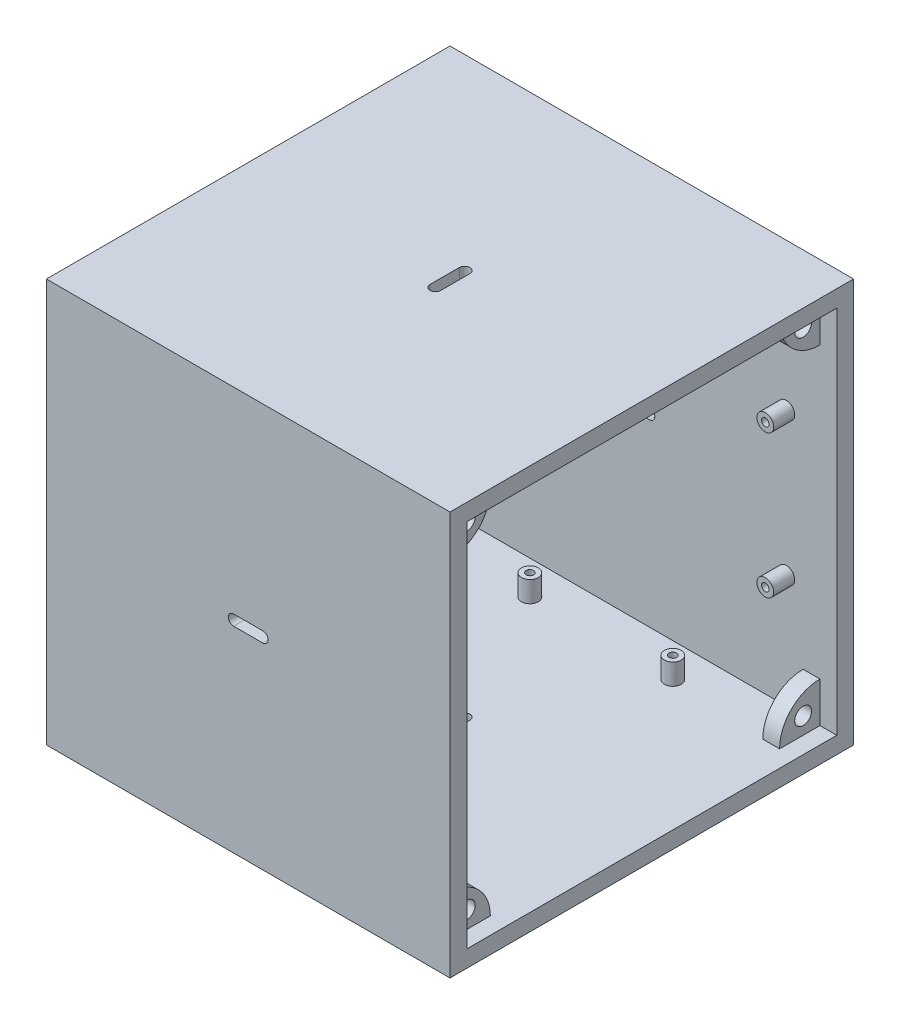
SolidWorks part; units mm, degrees
ref_plane "Front Plane" through (0, 0, 0) normal (0, 0, 1) x (1, 0, 0)
ref_plane "Top Plane" through (0, 0, 0) normal (0, 1, 0) x (1, 0, 0)
ref_plane "Right Plane" through (0, 0, 0) normal (1, 0, 0) x (0, 0, -1)
sketch "Sketch1" plane through (0, 0, 0) normal (0, 1, 0) x (1, 0, 0)
  line L1 (-76.2, -76.2) -> (76.2, -76.2)
  line L2 (-76.2, -76.2) -> (-76.2, 76.2)
  line L3 (-76.2, 76.2) -> (76.2, 76.2)
  line L4 (76.2, -76.2) -> (76.2, 76.2)
  line L5 (-76.2, -76.2) -> (76.2, 76.2) construction
  line L6 (-76.2, 76.2) -> (76.2, -76.2) construction
  point P0 (0, 0)
  dimension "D1" = 152.4
  dimension "D2" = 152.4
extrude "Boss-Extrude1" add sketch "Sketch1" along normal blind 152.4
shell "Shell2" thickness 6.35
ref_plane "Symmetry Top Plane" through (0, 76.2, 0) normal (0, 1, 0) x (1, 0, 0)
sketch "Sketch2" plane through (-69.85, 0, 0) normal (1, 0, 0) x (0, 0, -1)
  line L0 (-5.5, 76.2) -> (5.5, 76.2) construction
  line L1 (-7.5, 74.2) -> (7.5, 74.2) construction
  line L2 (-7.5, 74.2) -> (-7.5, 78.2) construction
  line L3 (-7.5, 78.2) -> (7.5, 78.2) construction
  line L4 (7.5, 74.2) -> (7.5, 78.2) construction
  line L5 (-7.5, 74.2) -> (7.5, 78.2)
  line L6 (-7.5, 78.2) -> (7.5, 74.2)
  line L7 (-5.5, 78.2) -> (5.5, 78.2)
  line L8 (-5.5, 74.2) -> (5.5, 74.2)
  line L10 (19, 73.2) -> (31, 73.2)
  line L11 (19, 73.2) -> (19, 79.2)
  line L12 (19, 79.2) -> (31, 79.2)
  line L13 (31, 73.2) -> (31, 79.2)
  line L14 (19, 73.2) -> (31, 79.2) construction
  line L15 (19, 79.2) -> (31, 73.2) construction
  line L16 (-31, 73.2) -> (-19, 73.2)
  line L17 (-31, 73.2) -> (-31, 79.2)
  line L18 (-31, 79.2) -> (-19, 79.2)
  line L19 (-19, 73.2) -> (-19, 79.2)
  line L20 (-31, 73.2) -> (-19, 79.2) construction
  line L21 (-31, 79.2) -> (-19, 73.2) construction
  arc A0 (-5.5, 78.2) -> (-5.5, 74.2) centre (-5.5, 76.2) ccw
  arc A1 (5.5, 74.2) -> (5.5, 78.2) centre (5.5, 76.2) ccw
  point P0 (0, 76.2)
  point P8 (0, 76.2)
  point P13 (-7.5, 76.2)
  point P14 (7.5, 76.2)
  point P15 (25, 76.2)
  point P20 (-25, 76.2)
  dimension "D6" = 2
  dimension "D1" = 15
  dimension "D2" = 4
  dimension "D3" = 76.2
  dimension "D4" = 0
  dimension "D5" = 25
  dimension "D7" = 15
  dimension "D8" = 12
  dimension "D9" = 6
  dimension "D10" = 25
  dimension "D11" = 25
  dimension "D12" = 6
  dimension "D13" = 12
  dimension "D14" = 25
extrude "Cut-Extrude3" cut sketch "Sketch2" along direction (1, 0, 0) on the side against the normal blind 6.35 contours L8 A1 L6 L5 A0 | L6 A1 L5 | L5 A1 L7 A0 L6 | L6 A0 L5 | L18 L19 L16 L17 | L12 L13 L10 L11
sketch "Sketch3" plane through (0, 0, -69.85) normal (0, 0, 1) x (1, 0, 0)
  line L0 (-5.5, 76.2) -> (5.5, 76.2) construction
  line L1 (-7.5, 74.2) -> (7.5, 74.2) construction
  line L2 (-7.5, 74.2) -> (-7.5, 78.2) construction
  line L3 (-7.5, 78.2) -> (7.5, 78.2) construction
  line L4 (7.5, 74.2) -> (7.5, 78.2) construction
  line L5 (-7.5, 74.2) -> (7.5, 78.2)
  line L6 (-7.5, 78.2) -> (7.5, 74.2)
  line L7 (-5.5, 78.2) -> (5.5, 78.2)
  line L8 (-5.5, 74.2) -> (5.5, 74.2)
  arc A0 (-5.5, 78.2) -> (-5.5, 74.2) centre (-5.5, 76.2) ccw
  arc A1 (5.5, 74.2) -> (5.5, 78.2) centre (5.5, 76.2) ccw
  point P0 (0, 76.2)
  point P7 (0, 76.2)
  point P12 (-7.5, 76.2)
  point P13 (7.5, 76.2)
  dimension "D3" = 2
  dimension "D6" = 76.2
  dimension "D1" = 15
  dimension "D2" = 4
  dimension "D4" = 15
  dimension "D5" = 0
extrude "Cut-Extrude4" cut sketch "Sketch3" against normal blind 6.35 contours L8 A1 L7 A0
sketch "Sketch4" plane through (0, 0, 69.85) normal (0, 0, -1) x (-1, 0, 0)
  line L0 (-5.5, 76.2) -> (5.5, 76.2) construction
  line L1 (-7.5, 74.2) -> (7.5, 74.2) construction
  line L2 (-7.5, 74.2) -> (-7.5, 78.2) construction
  line L3 (-7.5, 78.2) -> (7.5, 78.2) construction
  line L4 (7.5, 74.2) -> (7.5, 78.2) construction
  line L5 (-7.5, 74.2) -> (7.5, 78.2)
  line L6 (-7.5, 78.2) -> (7.5, 74.2)
  line L7 (-5.5, 78.2) -> (5.5, 78.2)
  line L8 (-5.5, 74.2) -> (5.5, 74.2)
  arc A0 (-5.5, 78.2) -> (-5.5, 74.2) centre (-5.5, 76.2) ccw
  arc A1 (5.5, 74.2) -> (5.5, 78.2) centre (5.5, 76.2) ccw
  point P0 (0, 76.2)
  point P7 (0, 76.2)
  point P12 (-7.5, 76.2)
  point P13 (7.5, 76.2)
  dimension "D3" = 2
  dimension "D1" = 15
  dimension "D2" = 4
  dimension "D4" = 15
  dimension "D5" = 0
  dimension "D6" = 76.2
extrude "Cut-Extrude5" cut sketch "Sketch4" against normal blind 6.35 contours L7 A1 L8 A0
sketch "Sketch5" plane through (0, 146.05, 0) normal (0, -1, 0) x (1, 0, 0)
  line L0 (0, -5.5) -> (0, 5.5) construction
  line L1 (-2, -5.5) -> (-2, 5.5)
  line L2 (2, -5.5) -> (2, 5.5)
  arc A0 (-2, -5.5) -> (2, -5.5) centre (0, -5.5) ccw
  arc A1 (2, 5.5) -> (-2, 5.5) centre (0, 5.5) ccw
  point P2 (0, 0)
  point P8 (0, -7.5)
  point P9 (0, 7.5)
  dimension "D1" = 15
  dimension "D2" = 4
extrude "Cut-Extrude6" cut sketch "Sketch5" against normal blind 6.35
mirror "Mirror1" about plane through (0, 76.2, 0) normal (0, 1, 0) of "Cut-Extrude6"
sketch "Sketch6" plane through (0, 146.05, 0) normal (0, -1, 0) x (1, 0, 0)
  line L0 (76.2, -76.2) -> (69.85, -76.2) construction
  line L1 (76.2, -76.2) -> (-76.2, -76.2) construction
  line L3 (69.85, -76.2) -> (63.5, -76.2)
  line L4 (69.85, -76.2) -> (69.85, 76.2)
  line L5 (69.85, 76.2) -> (63.5, 76.2)
  line L6 (63.5, -76.2) -> (63.5, 76.2)
  dimension "D1" = 6.35
  dimension "D2" = 152.4
  dimension "D3" = 6.35
extrude "Boss-Extrude2" add sketch "Sketch6" along normal blind 139.7
sketch "Sketch7" plane through (69.85, 0, 0) normal (1, 0, 0) x (0, 0, -1)
  line L0 (-69.85, 146.05) -> (69.85, 146.05) construction
  line L1 (69.85, 146.05) -> (69.85, 6.35) construction
  line L2 (-69.85, 6.35) -> (-69.85, 146.05) construction
  line L3 (69.85, 146.05) -> (69.85, 6.35) construction
  line L4 (69.85, 6.35) -> (-69.85, 6.35) construction
  line L5 (69.85, 21.59) -> (69.85, 130.81)
  line L6 (54.61, 146.05) -> (-54.61, 146.05)
  line L7 (-69.85, 21.59) -> (-69.85, 130.81)
  line L8 (54.61, 6.35) -> (-54.61, 6.35)
  arc A0 (54.61, 146.05) -> (69.85, 130.81) centre (69.85, 146.05) ccw
  arc A1 (-54.61, 146.05) -> (-69.85, 130.81) centre (-69.85, 146.05) cw
  arc A2 (69.85, 21.59) -> (54.61, 6.35) centre (69.85, 6.35) ccw
  arc A3 (-69.85, 21.59) -> (-54.61, 6.35) centre (-69.85, 6.35) cw
  dimension "D1" = 15.24
  dimension "D2" = 15.24
  dimension "D3" = 15.24
  dimension "D4" = 15.24
extrude "Cut-Extrude7" cut sketch "Sketch7" against normal blind 6.35
sketch "Sketch8" plane through (69.85, 0, 0) normal (1, 0, 0) x (0, 0, -1)
  line L1 (76.835, 76.2) -> (-76.835, 76.2) construction
  line L2 (0, 83.82) -> (0, -83.82) construction
  circle A0 centre (63.5, 12.7) radius 3.175
  circle A1 centre (63.5, 139.7) radius 3.175
  circle A2 centre (-63.5, 139.7) radius 3.175
  circle A3 centre (-63.5, 12.7) radius 3.175
  point P5 (63.4563, 12.9858)
  dimension "D1" = 6.35
  dimension "D2" = 6.35
  dimension "D3" = 6.35
extrude "Cut-Extrude8" cut sketch "Sketch8" against normal blind 6.35
sketch "Sketch9" plane through (-76.2, 0, 0) normal (-1, 0, 0) x (0, 0, 1)
  text T0 "<b>BUZZ BOX</b>" font "Century Schoolbook" height in points 48
  text T1 "GEORGIA INSTITUTE OF TECHNOLOGY"
  text T2 "ELECTRICAL & COMPUTER ENGINEERING"
  dimension "D1" = 28.4897
  dimension "D2" = 33.3824
  dimension "D3" = 30.4352
  dimension "D4" = 44.7282
  dimension "D5" = 36.5182
  dimension "D6" = 26.9956
extrude "Cut-Extrude9" cut sketch "Sketch9" against normal blind 0.3175
sketch "Sketch10" plane through (0, 0, 69.85) normal (0, 0, -1) x (-1, 0, 0)
  circle A1 centre (-57.15, 49.2125) radius 1.4288
  circle A2 centre (57.15, 49.2125) radius 1.4288
  circle A3 centre (-57.15, 103.1875) radius 1.4288
  circle A6 centre (57.15, 103.1875) radius 1.4287
  circle A7 centre (-57.15, 103.1875) radius 3.175
  circle A8 centre (-57.15, 49.2125) radius 3.175
  circle A9 centre (57.15, 49.2125) radius 3.175
  circle A10 centre (57.15, 103.1875) radius 3.175
  dimension "D1" = 114.3
  dimension "D3" = 2.8575
  dimension "D4" = 2.8575
  dimension "D5" = 2.8575
  dimension "D6" = 2.8575
  dimension "D13" = 6.35
  dimension "D14" = 6.35
  dimension "D15" = 6.35
  dimension "D16" = 6.35
  dimension "D2" = 53.975
  dimension "D7" = 114.3
  dimension "D8" = 53.975
  dimension "D9" = 57.15
  dimension "D10" = 49.2125
  dimension "D11" = 57.15
  dimension "D12" = 57.15
extrude "Boss-Extrude3" add sketch "Sketch10" along normal blind 7.9375
mirror "Mirror2" about plane through (0, 0, 0) normal (0, 0, 1) of "Boss-Extrude3"
sketch "Sketch11" plane through (0, 6.35, 0) normal (0, 1, 0) x (1, 0, 0)
  circle A0 centre (26.9875, -57.15) radius 1.4288
  circle A1 centre (26.9875, 57.15) radius 1.4288
  circle A2 centre (-26.9875, -57.15) radius 1.4288
  circle A3 centre (-26.9875, 57.15) radius 1.4287
  circle A4 centre (-26.9875, -57.15) radius 3.175
  circle A5 centre (26.9875, -57.15) radius 3.175
  circle A6 centre (26.9875, 57.15) radius 3.175
  circle A7 centre (-26.9875, 57.15) radius 3.175
  dimension "D3" = 2.8575
  dimension "D4" = 2.8575
  dimension "D5" = 2.8575
  dimension "D6" = 2.8575
  dimension "D9" = 6.35
  dimension "D10" = 6.35
  dimension "D11" = 6.35
  dimension "D12" = 6.35
  dimension "D1" = 114.3
  dimension "D2" = 53.975
  dimension "D7" = 114.3
  dimension "D8" = 53.975
  dimension "D13" = 57.15
  dimension "D14" = 26.9875
  dimension "D15" = 26.9875
  dimension "D16" = 26.9875
extrude "Boss-Extrude4" add sketch "Sketch11" along normal blind 7.9375
mirror "Mirror3" about plane through (0, 76.2, 0) normal (0, 1, 0) of "Boss-Extrude4"
sketch "Sketch15" plane through (-69.85, 0, 0) normal (1, 0, 0) x (0, 0, -1)
  circle A0 centre (-57.15, 49.2125) radius 1.4288
  circle A1 centre (57.15, 49.2125) radius 1.4288
  circle A2 centre (-57.15, 103.1875) radius 1.4288
  circle A3 centre (57.15, 103.1875) radius 1.4287
  circle A4 centre (-57.15, 103.1875) radius 3.175
  circle A5 centre (-57.15, 49.2125) radius 3.175
  circle A6 centre (57.15, 49.2125) radius 3.175
  circle A7 centre (57.15, 103.1875) radius 3.175
  point P14 (-41.366, 94.4094)
  dimension "D3" = 2.8575
  dimension "D4" = 2.8575
  dimension "D5" = 2.8575
  dimension "D6" = 2.8575
  dimension "D9" = 6.35
  dimension "D10" = 6.35
  dimension "D11" = 6.35
  dimension "D12" = 6.35
  dimension "D1" = 114.3
  dimension "D2" = 53.975
  dimension "D7" = 114.3
  dimension "D8" = 53.975
  dimension "D13" = 57.15
  dimension "D14" = 49.2125
  dimension "D15" = 49.2125
  dimension "D16" = 49.2125
extrude "Boss-Extrude5" add sketch "Sketch15" along normal blind 7.9375
